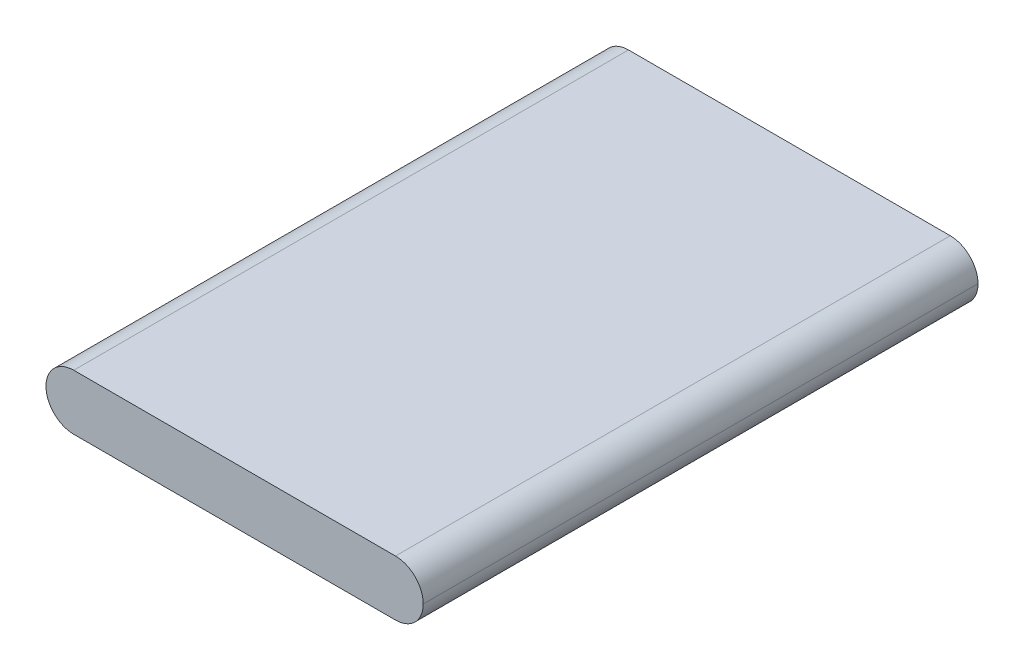
SolidWorks part; units mm, degrees
ref_plane "Front Plane" through (0, 0, 0) normal (0, 0, 1) x (1, 0, 0)
ref_plane "Top Plane" through (0, 0, 0) normal (0, 1, 0) x (1, 0, 0)
ref_plane "Right Plane" through (0, 0, 0) normal (1, 0, 0) x (0, 0, -1)
sketch "Sketch1" plane through (0, 0, 0) normal (0, 1, 0) x (1, 0, 0)
  line L1 (-17, -25) -> (17, -25)
  line L2 (-17, -25) -> (-17, 25)
  line L3 (-17, 25) -> (17, 25)
  line L4 (17, -25) -> (17, 25)
  line L5 (-17, -25) -> (17, 25) construction
  line L6 (-17, 25) -> (17, -25) construction
  point P0 (0, 0)
  dimension "D1" = 34
  dimension "D2" = 50
extrude "Boss-Extrude1" add sketch "Sketch1" along normal blind 5
fillet "Fillet1" radius 2.5 4 edges at (-17, 5, 0) (-17, 0, 0) (17, 0, 0) (17, 5, 0)
